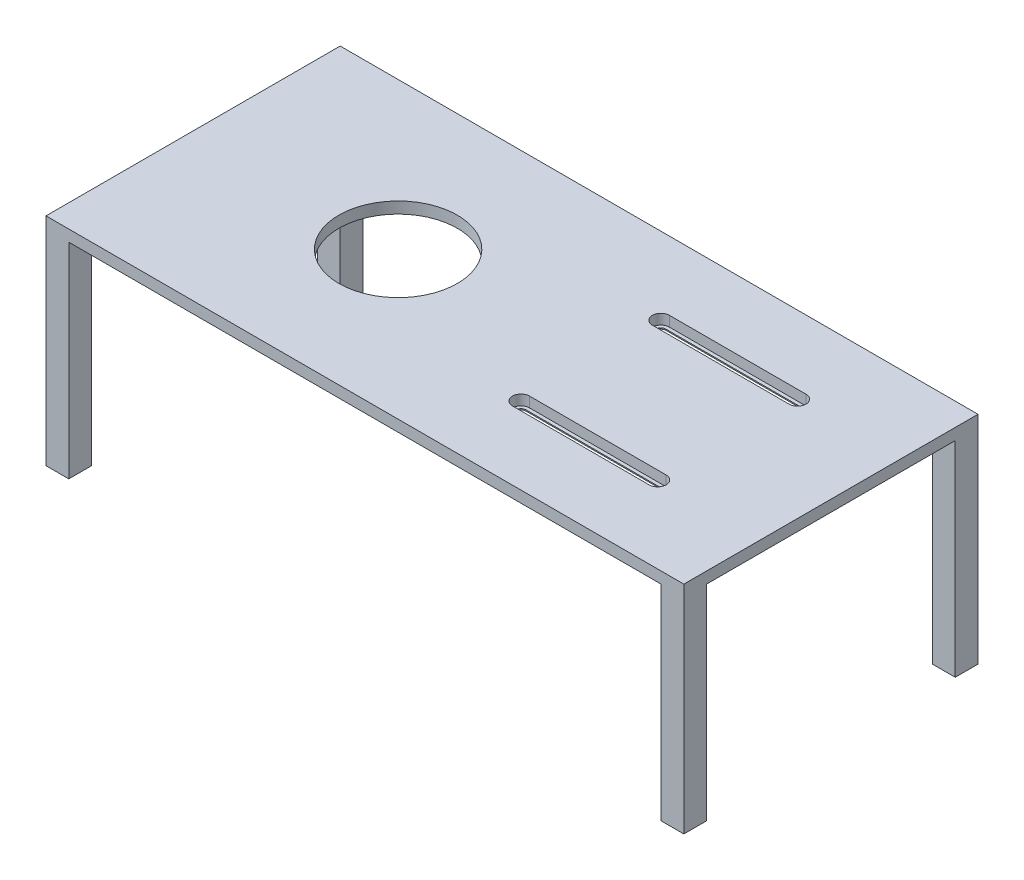
SolidWorks part; units mm, degrees
ref_plane "Płaszczyzna przednia" through (0, 0, 0) normal (0, 0, 1) x (1, 0, 0)
ref_plane "Płaszczyzna górna" through (0, 0, 0) normal (0, 1, 0) x (1, 0, 0)
ref_plane "Płaszczyzna prawa" through (0, 0, 0) normal (1, 0, 0) x (0, 0, -1)
sketch "Szkic1" plane through (0, 0, 0) normal (0, 1, 0) x (1, 0, 0)
  line L1 (0, 0) -> (280, 0)
  line L2 (0, 0) -> (0, 129.1357)
  line L3 (0, 129.1357) -> (280, 129.1357)
  line L4 (280, 0) -> (280, 129.1357)
  line L5 (0, 64.5678) -> (280, 64.5678) construction
  line L6 (0, 119.1357) -> (10, 119.1357)
  line L7 (10, 119.1357) -> (10, 129.1357)
  line L8 (270, 119.1357) -> (270, 129.1357)
  line L9 (280, 119.1357) -> (270, 119.1357)
  line L10 (280, 10) -> (270, 10)
  line L11 (270, 10) -> (270, 0)
  line L12 (10, 10) -> (10, 0)
  line L13 (0, 10) -> (10, 10)
  circle A0 centre (90, 64.5678) radius 26
  circle A1 centre (90, 64.5678) radius 15
  dimension "D5" = 52
  dimension "D6" = 30
  dimension "D1" = 280
  dimension "D2" = 190
  dimension "D3" = 10
  dimension "D4" = 10
extrude "Dodanie-wyciągnięcie1" add sketch "Szkic1" along normal blind 5 contours L5 L2 L13 L12 L1 L11 L10 L4 A0 | L2 L5 A0 L4 L9 L8 L3 L7 L6 region at (143.1571, 0, -31.2667) region at (143.1571, 0, -97.869)
extrude "Dodanie-wyciągnięcie2" add sketch "Szkic1<3>" along normal blind 5 and the other way blind 90 contours L13 L2 L1 L12 | L10 L11 L1 L4 | L9 L4 L3 L8 | L6 L7 L3 L2 region at (5, 0, -5) region at (275, 0, -5) region at (5, 0, -124.1357) region at (275, 0, -124.1357)
sketch "Szkic1<3>" plane through (0, 0, 0) normal (0, 1, 0) x (1, 0, 0) same geometry as "Szkic1"
sketch "Szkic2" plane through (0, 5, 0) normal (0, 1, 0) x (1, 0, 0)
  line L0 (116, 64.5678) -> (280, 64.5678) construction
  line L1 (280, 0) -> (280, 129.1357) construction
  line L2 (174.6345, 95.2678) -> (234.6345, 95.2678) construction
  line L3 (174.6345, 97.5178) -> (234.6345, 97.5178)
  line L4 (174.6345, 93.0178) -> (234.6345, 93.0178)
  line L5 (174.6345, 33.8678) -> (234.6345, 33.8678) construction
  line L6 (174.6345, 31.6178) -> (234.6345, 31.6178)
  line L7 (174.6345, 36.1178) -> (234.6345, 36.1178)
  line L8 (174.6345, 95.2678) -> (234.6345, 95.2678) construction
  line L9 (174.6345, 99.0178) -> (234.6345, 99.0178)
  line L10 (174.6345, 91.5178) -> (234.6345, 91.5178)
  line L11 (174.6345, 33.8678) -> (234.6345, 33.8678) construction
  line L12 (174.6345, 30.1178) -> (234.6345, 30.1178)
  line L13 (174.6345, 37.6178) -> (234.6345, 37.6178)
  circle A0 centre (90, 64.5678) radius 26 construction
  arc A1 (174.6345, 97.5178) -> (174.6345, 93.0178) centre (174.6345, 95.2678) ccw
  arc A2 (234.6345, 93.0178) -> (234.6345, 97.5178) centre (234.6345, 95.2678) ccw
  arc A3 (174.6345, 31.6178) -> (174.6345, 36.1178) centre (174.6345, 33.8678) cw
  arc A4 (234.6345, 36.1178) -> (234.6345, 31.6178) centre (234.6345, 33.8678) cw
  arc A5 (174.6345, 99.0178) -> (174.6345, 91.5178) centre (174.6345, 95.2678) ccw
  arc A6 (234.6345, 91.5178) -> (234.6345, 99.0178) centre (234.6345, 95.2678) ccw
  arc A7 (174.6345, 30.1178) -> (174.6345, 37.6178) centre (174.6345, 33.8678) cw
  arc A8 (234.6345, 37.6178) -> (234.6345, 30.1178) centre (234.6345, 33.8678) cw
  point P8 (204.6345, 95.2678)
  point P15 (204.6345, 33.8678)
  point P22 (204.6345, 95.2678)
  dimension "D1" = 4.5
  dimension "D2" = 7.5
  dimension "D3" = 60
  dimension "D4" = 61.4
extrude "Wytnij-wyciągnięcie1" cut sketch "Szkic2" against normal through all contours L4 A2 L3 A1 | A4 L7 A3 L6 region at (204.6345, 5, -95.2678) region at (204.6345, 5, -33.8678)
extrude "Wytnij-wyciągnięcie2" cut sketch "Szkic2<3>" against normal blind 4.5
sketch "Szkic2<3>" plane through (0, 5, 0) normal (0, 1, 0) x (1, 0, 0) same geometry as "Szkic2"
